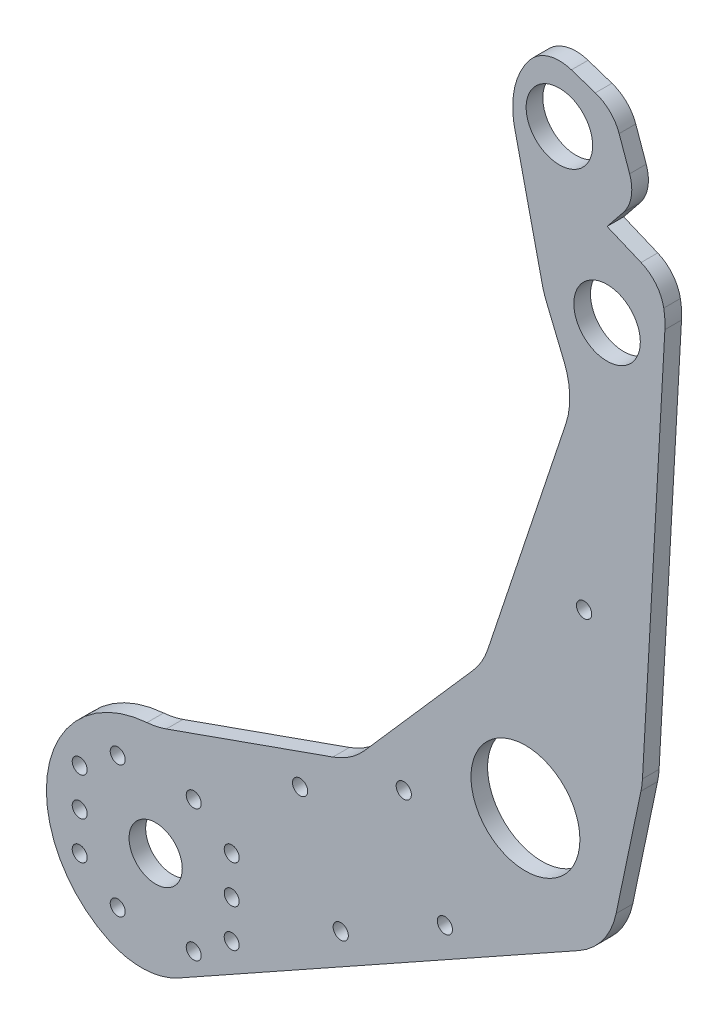
SolidWorks part; units mm, degrees
ref_plane "Front Plane" through (0, 0, 0) normal (0, 0, 1) x (1, 0, 0)
ref_plane "Top Plane" through (0, 0, 0) normal (0, 1, 0) x (1, 0, 0)
ref_plane "Right Plane" through (0, 0, 0) normal (1, 0, 0) x (0, 0, -1)
sketch "Sketch1" plane through (0, 0, 0) normal (0, 0, 1) x (1, 0, 0)
  line L0 (198.8616, 69.616) -> (188.9649, 57.2856)
  line L1 (38.107, -163.0696) -> (103.5814, -139.8861)
  line L2 (103.5814, -139.8861) -> (147.5504, -89.7457)
  line L3 (147.5504, -89.7457) -> (171.8362, -16.8147)
  line L4 (171.8362, -16.8147) -> (178.1894, 2.2642)
  line L5 (178.1894, 2.2642) -> (167.83, 27.4472)
  line L6 (157.4706, 73.0101) -> (157.4706, 93.39)
  line L7 (157.4706, 93.39) -> (170.6001, 98.791)
  line L8 (170.6001, 98.791) -> (190.928, 92.0219)
  line L9 (190.928, 92.0219) -> (198.8616, 69.616)
  line L10 (208.5808, 42.1673) -> (200.6841, -98.6168)
  line L11 (200.6841, -98.6168) -> (189.6112, -151.3856)
  line L12 (189.6112, -151.3856) -> (38.107, -236.12)
  line L13 (188.9649, 57.2856) -> (205.7114, 50.2708)
  line L14 (205.7114, 50.2708) -> (208.5808, 42.1673)
  line L15 (157.4706, 73.0101) -> (167.83, 27.4472)
  arc A9 (38.107, -163.0696) -> (38.107, -236.12) centre (38.107, -199.5948) ccw
  circle A10 centre (38.107, -199.5948) radius 8.89
  circle A11 centre (161.6863, -124.719) radius 18.2009
  circle A12 centre (188.9649, 29.3961) radius 11.1125
  circle A13 centre (173.036, 78.2376) radius 11.1125
  arc A18 (208.5805, 42.2939) -> (199.2278, 54.4816) centre (195.8806, 42.2306) ccw construction
  arc A19 (208.5405, 40.7376) -> (208.5805, 42.2939) centre (183.1808, 42.1673) ccw construction
  circle A20 centre (50.8212, -177.594) radius 2.5
  circle A21 centre (63.5212, -186.891) radius 2.5
  circle A22 centre (63.5212, -199.5948) radius 2.4962
  circle A23 centre (63.5212, -212.291) radius 2.5
  circle A24 centre (50.8212, -221.5881) radius 2.5
  circle A25 centre (25.4212, -221.5881) radius 2.5
  circle A26 centre (12.7212, -212.291) radius 2.5
  circle A27 centre (12.7212, -199.591) radius 2.5
  circle A28 centre (12.7212, -186.891) radius 2.5
  circle A29 centre (25.4212, -177.594) radius 2.5
  circle A30 centre (86.3812, -156.2331) radius 2.54
  circle A31 centre (121.0205, -139.8861) radius 2.54
  circle A32 centre (99.9584, -191.2205) radius 2.54
  circle A33 centre (134.7718, -172.0732) radius 2.54
  circle A34 centre (181.2818, -57.5003) radius 2.54
  point P33 (38.107, -199.5948)
  dimension "D1" = 22.225
  dimension "D2" = 22.225
  dimension "D5" = 73.0504
  dimension "D6" = 17.78
extrude "Boss-Extrude1" add sketch "Sketch1" along normal blind 5.5562
fillet "Fillet1" radius 25.4 11 edges at (157.4706, 93.39, 2.7781) (157.4706, 73.0101, 2.7781) (167.83, 27.4472, 2.7781) (178.1894, 2.2642, 2.7781) (147.5504, -89.7457, 2.7781) (103.5814, -139.8861, 2.7781) (38.107, -163.0696, 2.7781) (38.107, -236.12, 2.7781) (189.6112, -151.3856, 2.7781) (200.6841, -98.6168, 2.7781) (208.5808, 42.1673, 2.7781)
fillet "Fillet3" radius 12.7 2 edges at (190.928, 92.0219, 2.7781) (170.6001, 98.791, 2.7781)
fillet "Fillet4" radius 12.7 2 edges at (205.7114, 50.2708, 2.7781) (198.8616, 69.616, 2.7781)
